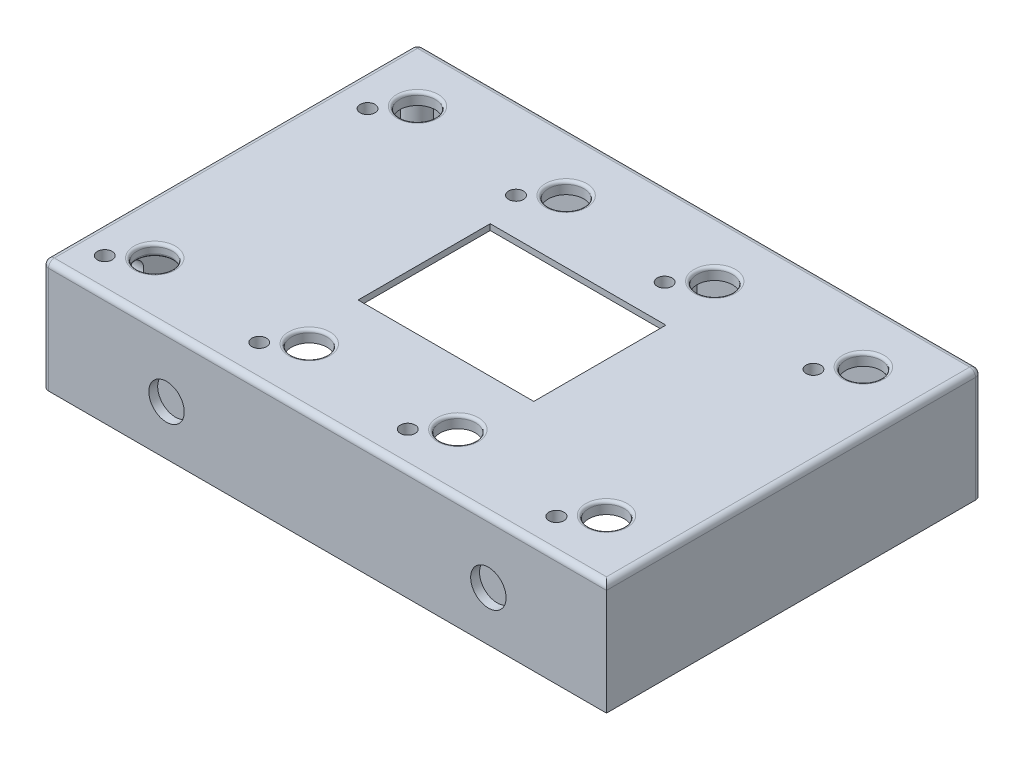
SolidWorks part; units mm, degrees
ref_plane "Front Plane" through (0, 0, 0) normal (0, 0, 1) x (1, 0, 0)
ref_plane "Top Plane" through (0, 0, 0) normal (0, 1, 0) x (1, 0, 0)
ref_plane "Right Plane" through (0, 0, 0) normal (1, 0, 0) x (0, 0, -1)
sketch "Sketch3" plane through (0, 0, 0) normal (0, 1, 0) x (1, 0, 0)
sketch "Sketch11" plane through (0, 0, 0) normal (0, 1, 0) x (1, 0, 0)
  line L1 (-91.5, 59.5) -> (91.5, 59.5)
  line L2 (-91.5, 59.5) -> (-91.5, -59.5)
  line L3 (-91.5, -59.5) -> (91.5, -59.5)
  line L4 (91.5, 59.5) -> (91.5, -59.5)
  line L5 (-91.5, 59.5) -> (91.5, -59.5) construction
  line L6 (-91.5, -59.5) -> (91.5, 59.5) construction
  point P0 (0, 0)
  dimension "D1" = 183
  dimension "D2" = 119
extrude "Boss-Extrude2" add sketch "Sketch11" along normal blind 34
shell "Shell19" thickness 4 removed face at (0, 0, 0) outward yes
sketch "Sketch12" plane through (0, 0, 0) normal (0, -1, 0) x (-1, 0, 0)
  circle A0 centre (-89.2941, 57.1284) radius 4
  circle A1 centre (89.3018, 57.1284) radius 4
  circle A2 centre (89.3018, -56.8526) radius 4
  circle A4 centre (-89.2941, -56.8526) radius 4
  circle A5 centre (0, -56.8526) radius 4
  circle A6 centre (0, 57.1284) radius 4
  point P4 (90.7579, 58.6667)
  point P7 (90.7579, -56.0823)
  point P8 (90.7579, -58.7963)
  point P9 (0, 0)
  point P10 (89.3018, -56.8526)
  point P11 (0, 0)
  point P12 (0, 0)
  point P15 (-90.716, -58.7963)
  point P16 (89.3018, 57.1284)
  point P17 (0, 0)
  point P18 (-89.2941, 57.1284)
  point P19 (-89.2941, -56.8526)
  point P22 (0, -56.8526)
  point P25 (0, 57.1284)
extrude "Boss-Extrude4" add sketch "Sketch12" against normal blind 34
hole_wizard "#6-32 Tapped Hole1" positions "Sketch13" profile "Sketch14" tap size "#6-32" standard "ANSI Inch"
sketch "Sketch13" plane through (0, 0, 0) normal (0, -1, 0) x (-1, 0, 0)
  point P0 (-89.2941, 57.1284)
  point P3 (-89.2941, -56.8526)
  point P6 (0, -56.8526)
  point P8 (0, 57.1284)
  point P11 (89.3018, 57.1284)
  point P14 (89.3018, -56.8526)
sketch "Sketch14" plane through (89.2941, 0, -57.1284) normal (1, 0, 0) x (0, 0, -1)
  line L0 (0, 0) -> (0, 11.7827)
  line L1 (0, 11.7827) -> (1.3525, 10.97)
  line L2 (1.3525, 10.97) -> (1.3525, 0.8685)
  line L3 (1.3525, 0.8685) -> (2.3876, 0)
  line L5 (2.3876, 0) -> (0, 0)
  line L6 (-1.3525, 0.8685) -> (-2.3876, 0) construction
  line L10 (0, 11.7827) -> (-1.3526, 10.97) construction
  line L11 (0, -6.35) -> (0, 107.95) construction
  dimension "Tap Drill Dia." = 2.7051
  dimension "Tap Drill Depth" = 10.97
  dimension "Near C'Sink Dia." = 4.7752
  dimension "Near C'Sink Angle" = 100
  dimension "Drill Angle" = 118
cosmetic thread "Hole Thread1"
cosmetic thread "Hole Thread2"
cosmetic thread "Hole Thread3"
cosmetic thread "Hole Thread4"
cosmetic thread "Hole Thread5"
cosmetic thread "Hole Thread6"
fillet "Fillet1" radius 2 8 edges at (86.2955, 17, 59.5) (-95.5, 19, 63.5) (-95.5, 19, -63.5) (95.5, 19, -63.5) (-95.5, 38, 0) (0, 38, 63.5) (95.5, 38, 0) (0, 38, -63.5)
sketch "Sketch15" plane through (0, 0, 0) normal (0, 1, 0) x (1, 0, 0)
  line L0 (93.5, 61.5) -> (-93.5, 61.5) construction
  line L2 (-93.5, 61.5) -> (-93.5, -61.5) construction
  circle A0 centre (-76.5, 44.5) radius 6
  dimension "D1" = 17
  dimension "D2" = 17
extrude "Cut-Extrude2" cut sketch "Sketch15" along normal blind 153
fillet "Fillet2" radius 1 1 edges at (-76.5, 38, -38.5)
sketch "Sketch16" plane through (0, 38, 0) normal (0, 1, 0) x (1, 0, 0)
  line L0 (93.5, -61.5) -> (93.5, 61.5) construction
  line L1 (93.5, 61.5) -> (-93.5, 61.5) construction
  line L3 (-93.5, 61.5) -> (-93.5, -61.5) construction
  line L4 (-93.5, -61.5) -> (93.5, -61.5) construction
  line L6 (-29.75, 22.375) -> (29.75, 22.375)
  line L7 (-29.75, 22.375) -> (-29.75, -22.375)
  line L8 (-29.75, -22.375) -> (29.75, -22.375)
  line L9 (29.75, 22.375) -> (29.75, -22.375)
  line L10 (-29.75, 22.375) -> (29.75, -22.375) construction
  line L11 (-29.75, -22.375) -> (29.75, 22.375) construction
  circle A0 centre (75.5, 43.5) radius 6
  circle A1 centre (-25.1667, 43.5) radius 6
  circle A2 centre (25.1633, 43.5) radius 6
  circle A3 centre (-76.5, 44.5) radius 7 construction
  circle A4 centre (-76.5, -44.5) radius 6
  circle A5 centre (75.5, -43.5) radius 6
  circle A6 centre (25.1633, -43.5) radius 6
  circle A7 centre (-25.1667, -43.5) radius 6
  point P0 (0, 0)
  point P30 (0, 0)
  dimension "D1" = 17
  dimension "D2" = 17
  dimension "D3" = 152.0033
  dimension "D4" = 50.3333
  dimension "D5" = 50.33
  dimension "D6" = 50.3367
  dimension "D7" = 17
  dimension "D8" = 17
  dimension "D9" = 44.75
  dimension "D10" = 59.5
extrude "Cut-Extrude3" cut sketch "Sketch16" against normal blind 153
fillet "Fillet3" radius 1 1 edges at (-25.1667, 38, -37.5)
fillet "Fillet4" radius 1 1 edges at (25.1633, 38, -37.5)
fillet "Fillet5" radius 1 1 edges at (75.5, 38, -37.5)
fillet "Fillet6" radius 1 1 edges at (-76.5, 34, 50.5)
fillet "Fillet7" radius 1 1 edges at (-76.5, 38, 50.5)
fillet "Fillet8" radius 1 1 edges at (-25.1667, 38, 49.5)
fillet "Fillet9" radius 1 1 edges at (25.1633, 38, 49.5)
fillet "Fillet10" radius 1 1 edges at (75.5, 38, 49.5)
sketch "Sketch17" plane through (0, 0, 63.5) normal (0, 0, 1) x (1, 0, 0)
  line L0 (-93.5, 36) -> (-93.5, 0) construction
  line L1 (95.5, 36) -> (95.5, 0) construction
  circle A0 centre (-53.5, 16.8239) radius 6
  circle A1 centre (55.5, 16.8239) radius 6
  point P0 (-51.3249, 16.8239)
  dimension "D1" = 40
  dimension "D2" = 40
sketch "Sketch19" plane through (0, 0, 0) normal (1, 0, 0) x (0, 0, -1)
  line L1 (5.2671, 25.9206) -> (19.2671, 25.9206)
  line L2 (5.2671, 25.9206) -> (5.2671, 17.6706)
  line L3 (5.2671, 17.6706) -> (19.2671, 17.6706)
  line L4 (19.2671, 25.9206) -> (19.2671, 17.6706)
  line L5 (5.2671, 25.9206) -> (19.2671, 17.6706) construction
  line L6 (5.2671, 17.6706) -> (19.2671, 25.9206) construction
  circle A1 centre (-37.2354, 21.7956) radius 4
  circle A3 centre (27.8443, 21.7956) radius 4
  point P0 (12.2671, 21.7956)
  point P9 (8.5359, 21.7956)
  point P10 (27.8443, 21.7956)
  point P11 (13.69, 21.7956)
  point P12 (12.2671, 21.7956)
  point P13 (-37.2354, 21.7956)
  dimension "D1" = 14
  dimension "D2" = 8.25
extrude "Cut-Extrude4" cut sketch "Sketch19" against normal blind 153
extrude "Cut-Extrude5" cut sketch "Sketch17" against normal blind 3
sketch "Sketch22" plane through (0, 34, 0) normal (0, -1, 0) x (-1, 0, 0)
  line L0 (29.75, -22.375) -> (-29.75, -22.375) construction
  line L1 (37.25, -24.725) -> (-32.35, -24.725)
  line L2 (37.25, -24.725) -> (37.25, 25.475)
  line L3 (37.25, 25.475) -> (-32.35, 25.475)
  line L4 (-32.35, -24.725) -> (-32.35, 25.475)
  line L7 (29.75, 22.375) -> (29.75, -22.375) construction
  dimension "D1" = 50.2
  dimension "D2" = 69.6
  dimension "D3" = 2.35
  dimension "D4" = 7.5
extrude "Cut-Extrude6" cut sketch "Sketch22" against normal blind 2
sketch "Sketch23" plane through (0, 34, 0) normal (0, -1, 0) x (-1, 0, 0)
  circle A0 centre (85.6494, -52.2646) radius 2.5
  circle A1 centre (76.5, -44.5) radius 7 construction
  circle A2 centre (34.0555, -51.5616) radius 2.5
  circle A3 centre (-16.5654, -51.8711) radius 2.5
  circle A4 centre (-67.3137, -52.2741) radius 2.5368
  circle A5 centre (84.2826, 35.3659) radius 2.5
  circle A6 centre (33.7274, 35.0908) radius 2.5
  circle A7 centre (-16.9316, 34.7685) radius 2.5
  circle A8 centre (-67.7009, 34.3801) radius 2.5
  circle A9 centre (76.5, 44.5) radius 6 construction
  circle A10 centre (25.1667, -43.5) radius 6 construction
  circle A11 centre (-25.1633, -43.5) radius 6 construction
  circle A12 centre (-75.5, -43.5) radius 6 construction
  circle A13 centre (25.1667, 43.5) radius 6 construction
  circle A14 centre (-25.1633, 43.5) radius 6 construction
  circle A15 centre (-75.5, 43.5) radius 6 construction
  point P0 (84.5743, 35.0908)
  dimension "D1" = 12
  dimension "D2" = 12
  dimension "D3" = 12
  dimension "D4" = 12
  dimension "D5" = 12
  dimension "D6" = 12
  dimension "D7" = 12
  dimension "D8" = 12
extrude "Cut-Extrude7" cut sketch "Sketch23" against normal blind 12
